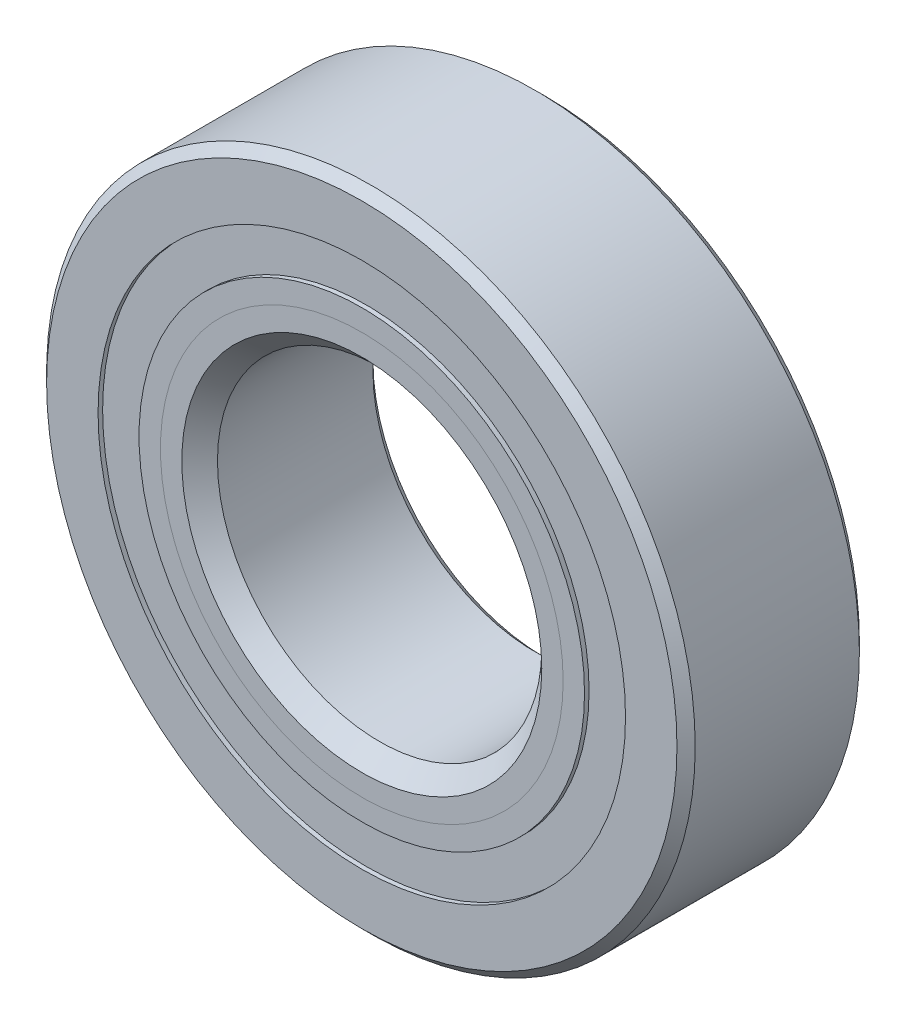
SolidWorks part; units mm, degrees
ref_plane "Front Plane" through (0, 0, 0) normal (0, 0, 1) x (1, 0, 0)
ref_plane "Top Plane" through (0, 0, 0) normal (0, 1, 0) x (1, 0, 0)
ref_plane "Right Plane" through (0, 0, 0) normal (1, 0, 0) x (0, 0, -1)
sketch "Sketch1" plane through (0, 0, 0) normal (1, 0, 0) x (0, 0, -1)
  line L0 (-7.1437, 0) -> (7.1437, 0) construction
  line L1 (0, 25.4) -> (0, -25.4) construction
  line L2 (6.4294, 25.4) -> (-6.4294, 25.4)
  line L3 (-6.4294, 25.4) -> (-7.1438, 24.6856)
  line L4 (-7.1438, 24.6856) -> (-7.1438, 20.6549)
  line L5 (-7.1438, 20.6549) -> (-3.175, 20.6549)
  line L6 (7.1438, 20.6549) -> (3.175, 20.6549)
  line L7 (7.1438, 24.6856) -> (7.1438, 20.6549)
  line L8 (6.4294, 25.4) -> (7.1438, 24.6856)
  line L9 (0, 25.4) -> (0, 19.05) construction
  line L10 (0, 19.05) -> (0, 12.7) construction
  arc A0 (-3.175, 20.6549) -> (3.175, 20.6549) centre (0, 19.05) cw
  point P14 (0, 12.7)
  dimension "Width" = 14.2875
  dimension "OD" = 50.8
  dimension "D1" = 45
  dimension "D2" = 0.7144
  dimension "D3" = 6.35
  dimension "D4" = 1.6049
revolve "Revolve1" add sketch "Sketch1" angle 360 about L0
sketch "Sketch2" plane through (0, 0, 0) normal (1, 0, 0) x (0, 0, -1)
  line L0 (-7.1438, 17.4451) -> (-3.175, 17.4451)
  line L1 (-7.1438, 24.6856) -> (-7.1438, -24.6856) construction
  line L2 (-7.1438, 17.4451) -> (-7.1438, 15.7706)
  line L3 (-7.1438, 15.7706) -> (-5.4693, 14.0962)
  line L4 (-5.4693, 14.0962) -> (0, 14.0962)
  line L5 (0, 25.4) -> (0, -25.4) construction
  line L6 (0, 14.0962) -> (0, 15.4924)
  line L7 (0, 15.4924) -> (0, 12.7) construction
  line L8 (-7.1438, 17.4451) -> (-7.1438, 14.0962) construction
  line L9 (-7.1438, 14.0962) -> (-5.4693, 14.0962) construction
  arc A0 (-3.175, 17.4451) -> (0, 15.4924) centre (0, 19.05) ccw
  arc A1 (3.175, 20.6549) -> (-3.175, 20.6549) centre (0, 19.05) ccw construction
  circle A2 centre (0, 19.05) radius 3.5576 construction
  dimension "D1" = 45
revolve "Revolve2" add sketch "Sketch2" angle 360 about L0
sketch "Sketch3" plane through (0, 0, 0) normal (1, 0, 0) x (0, 0, -1)
  line L0 (-7.1438, 15.7706) -> (-5.4693, 14.0962)
  line L1 (-5.4693, 14.0962) -> (0, 14.0962)
  line L2 (0, 14.0962) -> (0, 15.4924)
  line L3 (-7.1438, 15.7706) -> (-7.1438, 14.0962)
  line L4 (-7.1438, 17.4451) -> (-7.1438, 14.0962) construction
  line L5 (-7.1438, 14.0962) -> (-5.7475, 12.7)
  line L6 (-5.7475, 12.7) -> (6.4294, 12.7)
  line L7 (6.4294, 25.4) -> (6.4294, -25.4) construction
  line L8 (6.4294, 12.7) -> (7.1438, 13.4144)
  line L9 (7.1438, -24.6856) -> (7.1438, 24.6856) construction
  line L10 (7.1438, 13.4144) -> (7.1438, 17.4451)
  line L11 (7.1438, 17.4451) -> (3.175, 17.4451)
  line L13 (6.4294, 25.4) -> (7.1438, 24.6856) construction
  circle A0 centre (0, 19.05) radius 3.5576 construction
  arc A1 (3.175, 17.4451) -> (0, 15.4924) centre (0, 19.05) cw
revolve "Revolve3" add sketch "Sketch3" angle 360 about L0
sketch "Sketch4" plane through (0, 0, 0) normal (1, 0, 0) x (0, 0, -1)
  line L0 (-3.5576, 19.05) -> (3.5576, 19.05)
  circle A1 centre (0, 19.05) radius 3.5576 construction
  arc A2 (-3.5576, 19.05) -> (3.5576, 19.05) centre (0, 19.05) cw
  arc A3 (3.175, 20.6549) -> (-3.175, 20.6549) centre (0, 19.05) ccw construction
revolve "Revolve4" add sketch "Sketch4" angle 360 about L0
ref_axis "Axis1" through (0, 0, -7.1437) along (0, 0, 1)
pattern_circular "CirPattern1" count 12 every 30 about axis through (0, 0, -7.1437) along (0, 0, 1) of bodies 104
sketch "Sketch5" plane through (0, 0, 0) normal (1, 0, 0) x (0, 0, -1)
  line L0 (-7.1438, 20.6549) -> (-3.175, 20.6549) construction
  line L1 (-6.7866, 20.6549) -> (-3.5576, 20.6549)
  line L2 (-6.7866, 20.6549) -> (-6.7866, 17.4451)
  line L3 (-6.7866, 17.4451) -> (-3.5576, 17.4451)
  line L4 (-3.5576, 20.6549) -> (-3.5576, 17.4451)
  line L5 (-7.1438, 17.4451) -> (-3.175, 17.4451) construction
  line L6 (-6.4294, 25.4) -> (-7.1438, 24.6856) construction
  line L7 (0, 25.4) -> (0, 12.7) construction
  line L8 (6.7866, 17.4451) -> (3.5576, 17.4451)
  line L9 (3.5576, 20.6549) -> (3.5576, 17.4451)
  line L10 (6.7866, 20.6549) -> (3.5576, 20.6549)
  line L11 (6.7866, 20.6549) -> (6.7866, 17.4451)
  circle A0 centre (0, 19.05) radius 3.5576 construction
  point P10 (-6.7866, 25.0428)
revolve "Revolve5" add sketch "Sketch5" angle 360 about L0
equation "\"D2@Sketch1\" = \"Width@Sketch1\"*.05"
equation "\"D3@Sketch1\" = \"Width@Sketch1\"/2.25"
equation "\"D4@Sketch1\" = (((\"OD@Sketch1\"-\"Width@Sketch1\")/2)/3.25)/3.5"
equation "\"D2@CirPattern1\" = 360/\"Balls@CirPattern1\""
